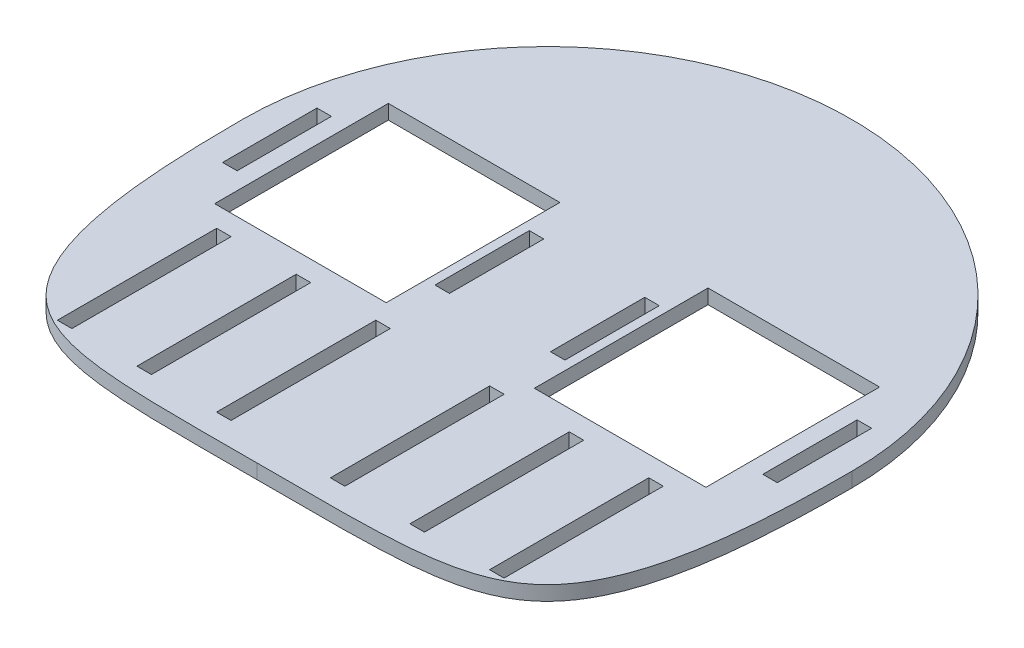
SolidWorks part; units mm, degrees
ref_plane "Front Plane" through (0, 0, 0) normal (0, 0, 1) x (1, 0, 0)
ref_plane "Top Plane" through (0, 0, 0) normal (0, 1, 0) x (1, 0, 0)
ref_plane "Right Plane" through (0, 0, 0) normal (1, 0, 0) x (0, 0, -1)
sketch "Sketch1" plane through (0, 0, 0) normal (0, 1, 0) x (1, 0, 0)
  line L0 (0, 0) -> (-157.9039, -157.9039) construction
  line L1 (0, -127) -> (0, 133.35) construction
  arc A0 (133.35, 0) -> (-133.35, 0) centre (0, 0) ccw
  spline S0 degree 3 poles (-133.35, 0) (-133.35, -51.198) (-123.8034, -129.8051) (-58.428, -127) (0, -127) knots 0 0 0 0 0.502616 1 1 1 1
  spline S1 degree 3 poles (133.35, 0) (133.35, -51.198) (123.8034, -129.8051) (58.428, -127) (0, -127) knots 0 0 0 0 0.502616 1 1 1 1
  dimension "D1" = 266.7
extrude "Base" add sketch "Sketch1" along normal blind 6.35
sketch "ShaftLayout" plane through (0, 6.35, 0) normal (0, 1, 0) x (1, 0, 0)
  line L0 (-133.35, 0) -> (133.35, 0) construction
  line L1 (0, 133.35) -> (0, -127) construction
  line L2 (-113.4353, -6.35) -> (-103.5293, -6.35)
  line L3 (-36.3853, -38) -> (-94.3853, -38)
  line L4 (-36.3853, -38) -> (-36.3853, 38)
  line L5 (-36.3853, 38) -> (-94.3853, 38)
  line L6 (-94.3853, -38) -> (-94.3853, 38)
  line L7 (-36.3853, -38) -> (-94.3853, 38) construction
  line L8 (-36.3853, 38) -> (-94.3853, -38) construction
  line L9 (-100.7353, -15.875) -> (-103.5293, -15.875)
  line L10 (-100.7353, -15.875) -> (-100.7353, 15.875)
  line L11 (-100.7353, 15.875) -> (-103.5293, 15.875)
  line L12 (-103.5293, -15.875) -> (-103.5293, 15.875)
  line L13 (-100.7353, -15.875) -> (-103.5293, 15.875) construction
  line L14 (-100.7353, 15.875) -> (-103.5293, -15.875) construction
  line L15 (-113.4353, -6.35) -> (-113.4353, 6.35)
  line L16 (-103.5293, -6.35) -> (-103.5293, 6.35)
  line L17 (-113.4353, 6.35) -> (-103.5293, 6.35)
  line L18 (-113.4353, -6.35) -> (-103.5293, 6.35) construction
  line L19 (-103.5293, -6.35) -> (-113.4353, 6.35) construction
  line L20 (-115.0228, -9.525) -> (-113.4353, -9.525)
  line L21 (-115.0228, -9.525) -> (-115.0228, 9.525)
  line L22 (-113.4353, -9.525) -> (-113.4353, 9.525)
  line L23 (-115.0228, 9.525) -> (-113.4353, 9.525)
  line L24 (-115.0228, -9.525) -> (-113.4353, 9.525) construction
  line L25 (-113.4353, -9.525) -> (-115.0228, 9.525) construction
  line L26 (-126.1353, -7.9375) -> (-115.0228, -7.9375)
  line L27 (-126.1353, -7.9375) -> (-126.1353, 7.9375)
  line L28 (-115.0228, -7.9375) -> (-115.0228, 7.9375)
  line L29 (-126.1353, 7.9375) -> (-115.0228, 7.9375)
  line L30 (-126.1353, -7.9375) -> (-115.0228, 7.9375) construction
  line L31 (-115.0228, -7.9375) -> (-126.1353, 7.9375) construction
  line L32 (-17.3353, -7.9375) -> (-28.4478, -7.9375)
  line L33 (-30.0353, -9.525) -> (-28.4478, -9.525)
  line L34 (-30.0353, -9.525) -> (-30.0353, 9.525)
  line L35 (-30.0353, 9.525) -> (-28.4478, 9.525)
  line L36 (-28.4478, -9.525) -> (-28.4478, 9.525)
  line L37 (-30.0353, -9.525) -> (-28.4478, 9.525) construction
  line L38 (-30.0353, 9.525) -> (-28.4478, -9.525) construction
  line L39 (-17.3353, -7.9375) -> (-17.3353, 7.9375)
  line L40 (-28.4478, -7.9375) -> (-28.4478, 7.9375)
  line L41 (-17.3353, 7.9375) -> (-28.4478, 7.9375)
  line L42 (-17.3353, -7.9375) -> (-28.4478, 7.9375) construction
  line L43 (-28.4478, -7.9375) -> (-17.3353, 7.9375) construction
  arc A0 (133.35, 0) -> (-133.35, 0) centre (0, 0) ccw construction
  point P10 (-65.3853, 0)
  point P15 (-102.1323, 0)
  point P20 (-29.2416, 0)
  point P21 (-108.4823, 0)
  point P22 (-114.2291, 0)
  point P23 (-120.5791, 0)
  point P41 (-22.8916, 0)
  dimension "D1" = 58
  dimension "D2" = 76
  dimension "D3" = 6.35
  dimension "D4" = 2.794
  dimension "D5" = 31.75
  dimension "D6" = 9.906
  dimension "D7" = 12.7
  dimension "D8" = 19.05
  dimension "D9" = 1.5875
  dimension "D10" = 12.7
  dimension "D11" = 15.875
  dimension "D12" = 19.05
  dimension "D13" = 1.5875
  dimension "D14" = 15.875
  dimension "D15" = 12.7
  dimension "D16" = 6.35
sketch "MotorLayout" plane through (0, 6.35, 0) normal (0, 1, 0) x (1, 0, 0)
  line L0 (-97.7353, -81.74) -> (-117.7353, -81.74) construction
  line L1 (-97.7353, -110.24) -> (-21.7353, -110.24)
  line L2 (-97.7353, -110.24) -> (-97.7353, -53.24)
  line L3 (-97.7353, -53.24) -> (-21.7353, -53.24)
  line L4 (-21.7353, -110.24) -> (-21.7353, -53.24)
  line L5 (-97.7353, -110.24) -> (-21.7353, -53.24) construction
  line L6 (-97.7353, -53.24) -> (-21.7353, -110.24) construction
  line L7 (-113.4353, -92.0587) -> (-103.5293, -92.0587)
  line L8 (-103.5293, -97.615) -> (-100.7353, -97.615)
  line L9 (-103.5293, -97.615) -> (-103.5293, -65.865)
  line L10 (-103.5293, -65.865) -> (-100.7353, -65.865)
  line L11 (-100.7353, -97.615) -> (-100.7353, -65.865)
  line L12 (-103.5293, -97.615) -> (-100.7353, -65.865) construction
  line L13 (-103.5293, -65.865) -> (-100.7353, -97.615) construction
  line L14 (-36.3853, -38) -> (-94.3853, -38) construction
  line L15 (-113.4353, -92.0587) -> (-113.4353, -71.4212)
  line L16 (-103.5293, -92.0587) -> (-103.5293, -71.4212)
  line L17 (-113.4353, -71.4212) -> (-103.5293, -71.4212)
  line L18 (-113.4353, -92.0587) -> (-103.5293, -71.4212) construction
  line L19 (-103.5293, -92.0587) -> (-113.4353, -71.4212) construction
  line L20 (-102.1323, -1000) -> (-102.1323, 49000) construction
  point P0 (-59.7353, -81.74)
  point P7 (-102.1323, -81.74)
  point P14 (-108.4823, -81.74)
  dimension "D1" = 20
  dimension "D2" = 76
  dimension "D3" = 57
  dimension "D4" = 2.794
  dimension "D5" = 15.24
  dimension "D6" = 31.75
  dimension "D7" = 20.6375
  dimension "D8" = 12.7
  dimension "D9" = 3
sketch "Sketch6" plane through (0, 6.35, 0) normal (0, 1, 0) x (1, 0, 0)
  line L0 (-36.3853, -38) -> (-36.3853, 38) construction
  line L1 (-32.4166, -38) -> (-107.4981, -38)
  line L2 (-32.4166, -38) -> (-32.4166, 38)
  line L3 (-32.4166, 38) -> (-107.4981, 38)
  line L4 (-107.4981, -38) -> (-107.4981, 38)
  line L5 (-28.4478, -9.525) -> (-28.4478, 9.525) construction
  line L6 (-103.5293, -15.875) -> (-103.5293, 15.875) construction
  line L7 (0, 133.35) -> (0, -127) construction
  line L8 (28.4478, 20.6375) -> (22.0978, -20.6375) construction
  line L9 (28.4478, -20.6375) -> (22.0978, 20.6375) construction
  line L10 (115.0228, 20.6375) -> (121.3728, -20.6375) construction
  line L11 (115.0228, -20.6375) -> (121.3728, 20.6375) construction
  line L12 (-133.35, 0) -> (133.35, 0) construction
  line L13 (-115.0228, -20.6375) -> (-121.3728, -20.6375)
  line L14 (-115.0228, -20.6375) -> (-115.0228, 20.6375)
  line L15 (-115.0228, 20.6375) -> (-121.3728, 20.6375)
  line L16 (-121.3728, -20.6375) -> (-121.3728, 20.6375)
  line L17 (-115.0228, -20.6375) -> (-121.3728, 20.6375) construction
  line L18 (-115.0228, 20.6375) -> (-121.3728, -20.6375) construction
  line L19 (-115.0228, -9.525) -> (-115.0228, 9.525) construction
  line L20 (-126.1353, 7.9375) -> (-115.0228, 7.9375) construction
  line L21 (-17.3353, 7.9375) -> (-28.4478, 7.9375) construction
  line L22 (-28.4478, -20.6375) -> (-22.0978, -20.6375)
  line L23 (-28.4478, -20.6375) -> (-28.4478, 20.6375)
  line L24 (-28.4478, 20.6375) -> (-22.0978, 20.6375)
  line L25 (-22.0978, -20.6375) -> (-22.0978, 20.6375)
  line L26 (-28.4478, -20.6375) -> (-22.0978, 20.6375) construction
  line L27 (-28.4478, 20.6375) -> (-22.0978, -20.6375) construction
  line L28 (22.0978, -20.6375) -> (22.0978, 20.6375)
  line L29 (28.4478, 20.6375) -> (22.0978, 20.6375)
  line L30 (28.4478, -20.6375) -> (28.4478, 20.6375)
  line L31 (28.4478, -20.6375) -> (22.0978, -20.6375)
  line L32 (121.3728, -20.6375) -> (121.3728, 20.6375)
  line L33 (115.0228, 20.6375) -> (121.3728, 20.6375)
  line L34 (115.0228, -20.6375) -> (115.0228, 20.6375)
  line L35 (115.0228, -20.6375) -> (121.3728, -20.6375)
  line L36 (107.4981, -38) -> (107.4981, 38)
  line L37 (32.4166, 38) -> (107.4981, 38)
  line L38 (32.4166, -38) -> (32.4166, 38)
  line L39 (32.4166, -38) -> (107.4981, -38)
  point P16 (-118.1978, 0)
  point P27 (-25.2728, 0)
  point P44 (25.2728, 0)
  point P45 (118.1978, 0)
  dimension "D1" = 3.9688
  dimension "D2" = 3.9688
  dimension "D3" = 12.7
  dimension "D4" = 12.7
  dimension "D5" = 6.35
  dimension "D6" = 6.35
extrude "WheelShaftCut" cut sketch "Sketch6" against normal through all
sketch "Sketch8" plane through (0, 6.35, 0) normal (0, 1, 0) x (1, 0, 0)
  line L0 (-97.7353, -81.74) -> (-21.7353, -81.74) construction
  line L1 (-21.7353, -110.24) -> (-21.7353, -53.24) construction
  line L2 (-97.7353, -53.24) -> (-21.7353, -53.24) construction
  line L3 (-21.7353, -116.59) -> (-28.0853, -116.59)
  line L4 (-21.7353, -116.59) -> (-21.7353, -46.89)
  line L5 (-21.7353, -46.89) -> (-28.0853, -46.89)
  line L6 (-28.0853, -116.59) -> (-28.0853, -46.89)
  line L7 (-21.7353, -116.59) -> (-28.0853, -46.89) construction
  line L8 (-21.7353, -46.89) -> (-28.0853, -116.59) construction
  line L9 (-56.5603, -116.59) -> (-62.9103, -116.59)
  line L10 (-56.5603, -116.59) -> (-56.5603, -46.89)
  line L11 (-56.5603, -46.89) -> (-62.9103, -46.89)
  line L12 (-62.9103, -116.59) -> (-62.9103, -46.89)
  line L13 (-56.5603, -116.59) -> (-62.9103, -46.89) construction
  line L14 (-56.5603, -46.89) -> (-62.9103, -116.59) construction
  line L15 (-91.3853, -116.59) -> (-97.7353, -116.59)
  line L16 (-91.3853, -116.59) -> (-91.3853, -46.89)
  line L17 (-91.3853, -46.89) -> (-97.7353, -46.89)
  line L18 (-97.7353, -116.59) -> (-97.7353, -46.89)
  line L19 (-91.3853, -116.59) -> (-97.7353, -46.89) construction
  line L20 (-91.3853, -46.89) -> (-97.7353, -116.59) construction
  line L21 (-97.7353, -110.24) -> (-97.7353, -53.24) construction
  line L22 (0, 133.35) -> (0, -127) construction
  line L23 (91.3853, -46.89) -> (97.7353, -116.59) construction
  line L24 (91.3853, -116.59) -> (97.7353, -46.89) construction
  line L25 (56.5603, -46.89) -> (62.9103, -116.59) construction
  line L26 (56.5603, -116.59) -> (62.9103, -46.89) construction
  line L27 (21.7353, -46.89) -> (28.0853, -116.59) construction
  line L28 (21.7353, -116.59) -> (28.0853, -46.89) construction
  line L29 (97.7353, -81.74) -> (21.7353, -81.74) construction
  line L30 (97.7353, -116.59) -> (97.7353, -46.89)
  line L31 (91.3853, -46.89) -> (97.7353, -46.89)
  line L32 (91.3853, -116.59) -> (91.3853, -46.89)
  line L33 (91.3853, -116.59) -> (97.7353, -116.59)
  line L34 (62.9103, -116.59) -> (62.9103, -46.89)
  line L35 (56.5603, -46.89) -> (62.9103, -46.89)
  line L36 (56.5603, -116.59) -> (56.5603, -46.89)
  line L37 (56.5603, -116.59) -> (62.9103, -116.59)
  line L38 (28.0853, -116.59) -> (28.0853, -46.89)
  line L39 (21.7353, -46.89) -> (28.0853, -46.89)
  line L40 (21.7353, -116.59) -> (21.7353, -46.89)
  line L41 (21.7353, -116.59) -> (28.0853, -116.59)
  point P5 (-24.9103, -81.74)
  point P14 (-59.7353, -81.74)
  point P19 (-94.5603, -81.74)
  point P42 (94.5603, -81.74)
  point P43 (59.7353, -81.74)
  point P44 (24.9103, -81.74)
  dimension "D1" = 6.35
  dimension "D2" = 6.35
  dimension "D3" = 3
extrude "Cut-Extrude3" cut sketch "Sketch8" against normal through all
